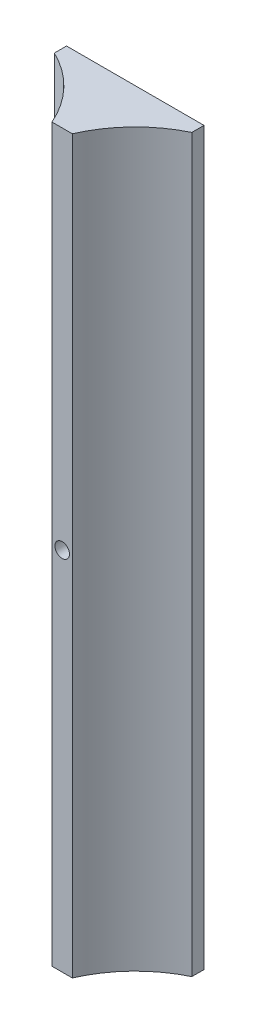
SolidWorks part; units mm, degrees
ref_plane "Front" through (0, 0, 0) normal (0, 0, 1) x (1, 0, 0)
ref_plane "Top" through (0, 0, 0) normal (0, 1, 0) x (1, 0, 0)
ref_plane "Right" through (0, 0, 0) normal (1, 0, 0) x (0, 0, -1)
sketch "Sketch1" plane through (0, 0, 0) normal (0, 1, 0) x (1, 0, 0)
  line L0 (-0.8348, 0) -> (0.8348, 0)
  line L1 (5.6411, 5) -> (5.6411, 6)
  line L2 (5.6411, 6) -> (-5.6411, 6)
  line L3 (-5.6411, 6) -> (-5.6411, 5)
  arc A0 (0.8348, 0) -> (5.6411, 5) centre (10, -4) cw
  arc A1 (-5.6411, 5) -> (-0.8348, 0) centre (-10, -4) cw
  point P9 (0, 6)
  point P10 (0, 0)
  dimension "D1" = 10
  dimension "D6" = 6
  dimension "D2" = 20
  dimension "D3" = 10
  dimension "D4" = 1
extrude "Boss-Extrude1" add sketch "Sketch1" along normal blind 60
sketch "Sketch3" plane through (0, 0, -6) normal (0, 0, -1) x (-1, 0, 0)
  line L0 (0, 0) -> (0, 60) construction
  line L1 (-5.6411, 0) -> (5.6411, 0) construction
  line L2 (-5.6411, 60) -> (5.6411, 60) construction
  point P6 (0, 30)
  dimension "D2" = 30
hole_wizard "Tapped Hole for M2.5x0.45 Helicoil1" positions "3DSketch1" profile "Sketch4" tap size "M2.5x0.45" standard "Helicoil® Metric"
sketch3d "3DSketch1"
  point P0 (0, 30, -6)
cosmetic thread "Hole Thread2" parameters "D1"=3, "D2"=3.145
sketch "Sketch4" plane through (0, 30, -6) normal (1, 0, 0) x (0, 1, 0)
  line L0 (0, 0) -> (0, 4.7661)
  line L1 (0, 4.7661) -> (1.275, 4)
  line L2 (1.275, 4) -> (1.275, 0)
  line L5 (1.275, 0) -> (0, 0)
  line L10 (0, 4.7661) -> (-1.275, 4) construction
  line L11 (0, -6.35) -> (0, 107.95) construction
  dimension "Tap Drill Dia." = 2.55
  dimension "Tap Drill Depth" = 4
  dimension "Drill Angle" = 118
hole_wizard "Ø1.2 (1.2) Diameter Hole1" positions "3DSketch2" profile "Sketch5" hole size "Ø1.2" standard "ANSI Metric"
sketch3d "3DSketch2"
  point P0 (0, 30, -6)
sketch "Sketch5" plane through (0, 30, -6) normal (1, 0, 0) x (0, 1, 0)
  line L0 (0, 0) -> (0, 6.8105)
  line L1 (0, 6.8105) -> (0.6, 6.45)
  line L2 (0.6, 6.45) -> (0.6, 0)
  line L5 (0.6, 0) -> (0, 0)
  line L10 (0, 6.8105) -> (-0.6, 6.45) construction
  line L11 (0, -6.35) -> (0, 107.95) construction
  dimension "Hole Dia." = 1.2
  dimension "Hole Depth" = 6.45
  dimension "Drill Angle" = 118
